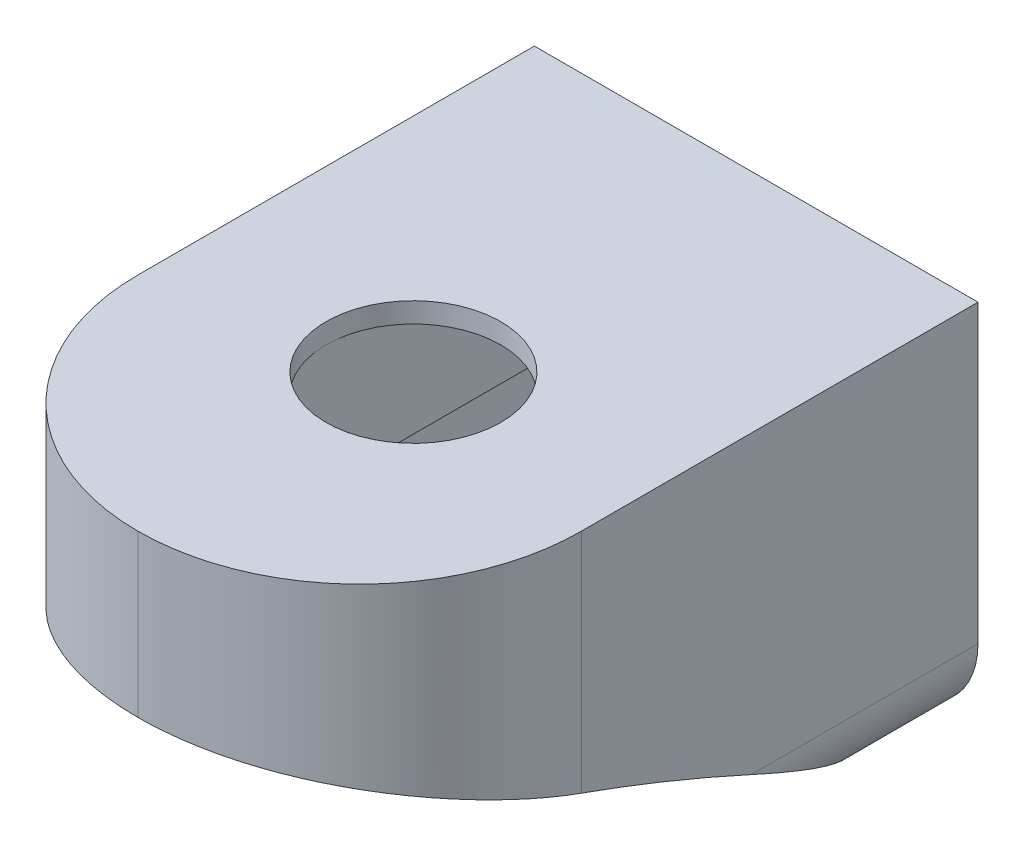
SolidWorks part; units mm, degrees
ref_plane "Front Plane" through (0, 0, 0) normal (0, 0, 1) x (1, 0, 0)
ref_plane "Top Plane" through (0, 0, 0) normal (0, 1, 0) x (1, 0, 0)
ref_plane "Right Plane" through (0, 0, 0) normal (1, 0, 0) x (0, 0, -1)
sketch "Sketch1" plane through (0, 0, 0) normal (0, 0, 1) x (1, 0, 0)
  line L1 (-16.5, 14) -> (16.5, 14)
  line L2 (-16.5, 14) -> (-16.5, -14)
  line L3 (-16.5, -14) -> (16.5, -14)
  line L4 (16.5, 14) -> (16.5, -14)
  line L5 (-16.5, 14) -> (16.5, -14) construction
  line L6 (-16.5, -14) -> (16.5, 14) construction
  point P0 (0, 0)
  dimension "D1" = 33
  dimension "D2" = 28
extrude "Boss-Extrude1" add sketch "Sketch1" along normal blind 46
sketch "Sketch3" plane through (16.5, 0, 0) normal (1, 0, 0) x (0, 0, -1)
  line L1 (-46, -14) -> (-46, 14) construction
  line L2 (-46, -14) -> (0, -14) construction
  line L3 (-5, -14) -> (-46, -14)
  line L4 (-46, -14) -> (-46, 2)
  spline S0 degree 2 poles (-46, 2) (-24.5909, -3.0891) (-5, -14) knots 0 0 0 1 1 1
  dimension "D1" = 5
  dimension "D2" = 12
extrude "Cut-Extrude1" cut sketch "Sketch3" against normal through all
sketch "Sketch4" plane through (16.5, 0, 0) normal (1, 0, 0) x (0, 0, -1)
  line L0 (-5, -14) -> (-2.5, -14)
  line L1 (-5, -14) -> (0, -14) construction
  line L2 (-2.5, -14) -> (-2.5, 3.5)
  line L3 (-2.5, 3.5) -> (-40.5, 3.5)
  line L4 (-40.5, 3.5) -> (-40.5, 0.5883)
  parabola Q0 (-5, -14) -> (-46, 2) focus (-58.9654, -76.3317) apex (-35.4091, -0.9084) construction
  parabola Q1 (-5, -14) -> (-46, 2) focus (-58.9654, -76.3317) apex (-35.4091, -0.9084) construction
  parabola Q2 (-5, -14) -> (-40.5, 0.5883) focus (-58.9654, -76.3317) apex (-35.4091, -0.9084)
  dimension "D1" = 38
  dimension "D2" = 17.5
extrude "Cut-Extrude2" cut sketch "Sketch4" against normal blind 27 from offset 3 offset against normal yes
fillet "Fillet1" radius 12.5 2 edges at (13.5, 2.0441, 40.5) (-13.5, 2.0441, 40.5)
fillet "Fillet2" radius 16.5 2 edges at (16.5, 8, 46) (-16.5, 8, 46)
fillet "Fillet3" radius 6 2 edges at (-16.5, -14, 2.5) (16.5, -14, 2.5)
sketch "Sketch5" plane through (0, 3.5, 0) normal (0, -1, 0) x (1, 0, 0)
  line L0 (0, 0) -> (0, 46) construction
  line L1 (-13.5, 2.5) -> (13.5, 2.5) construction
  line L2 (-6.5, 9) -> (6.5, 9)
  line L3 (-6.5, 9) -> (-6.5, 32)
  line L4 (-6.5, 32) -> (6.5, 32)
  line L5 (6.5, 9) -> (6.5, 32)
  line L6 (-6.5, 9) -> (6.5, 32) construction
  line L7 (-6.5, 32) -> (6.5, 9) construction
  point P4 (0, 20.5)
  dimension "D1" = 6.5
  dimension "D2" = 23
  dimension "D3" = 13
extrude "Cut-Extrude3" cut sketch "Sketch5" against normal blind 9
sketch "Sketch6" plane through (0, 12.5, 0) normal (0, -1, 0) x (1, 0, 0)
  line L0 (0, 32) -> (0, 9) construction
  line L1 (6.5, 32) -> (-6.5, 32) construction
  line L2 (-6.5, 9) -> (6.5, 9) construction
  circle A0 centre (0, 25.5) radius 6.5
  dimension "D1" = 13
extrude "Cut-Extrude5" cut sketch "Sketch6" against normal through all
sketch "Sketch7" plane through (0, 3.5, 0) normal (0, -1, 0) x (1, 0, 0)
  line L0 (-6.5, 20.5) -> (6.5, 20.5) construction
  line L1 (-6.5, 32) -> (-6.5, 9) construction
  line L2 (6.5, 9) -> (6.5, 32) construction
  line L3 (0, 6.7) -> (0, 34.3) construction
  circle A1 centre (0, 34.3) radius 1
  circle A2 centre (0, 6.7) radius 1
  point P10 (0, 20.5)
  point P12 (0, 0)
  dimension "D2" = 2
  dimension "D1" = 27.6
extrude "Cut-Extrude6" cut sketch "Sketch7" against normal blind 8
sketch "Sketch8" plane through (0, 0, 0) normal (0, 0, -1) x (-1, 0, 0)
  line L0 (0, 0) -> (-16.5, 0) construction
  line L1 (-16.5, -8) -> (-16.5, 14) construction
  circle A0 centre (-9.5, 0) radius 1.3
  circle A1 centre (-5, 0) radius 2.5
  circle A2 centre (-0.5, 0) radius 1.3
  dimension "D1" = 2.6
  dimension "D2" = 5
  dimension "D4" = 9
  dimension "D5" = 4.5
  dimension "D3" = 11.5
extrude "Cut-Extrude7" cut sketch "Sketch8" against normal up to surface (2.5 mm away) up to face at (0, -7.9645, 2.5)
